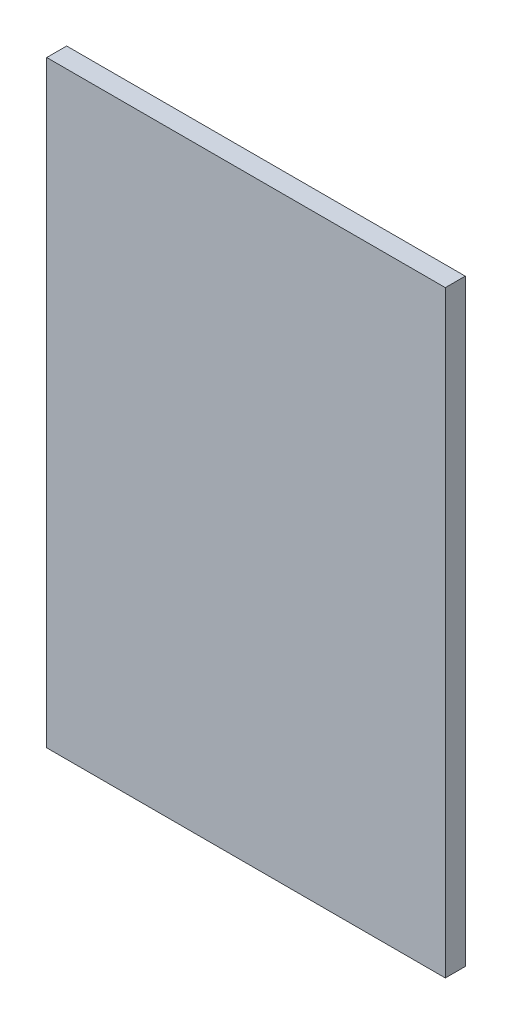
SolidWorks part; units mm, degrees
ref_plane "Front Plane" through (0, 0, 0) normal (0, 0, 1) x (1, 0, 0)
ref_plane "Top Plane" through (0, 0, 0) normal (0, 1, 0) x (1, 0, 0)
ref_plane "Right Plane" through (0, 0, 0) normal (1, 0, 0) x (0, 0, -1)
sketch "Sketch1" plane through (0, 0, 0) normal (0, 0, 1) x (1, 0, 0)
  line L1 (0, 0) -> (200, 0)
  line L2 (0, 0) -> (0, 300)
  line L3 (0, 300) -> (200, 300)
  line L4 (200, 0) -> (200, 300)
  dimension "D1" = 200
  dimension "D2" = 300
extrude "Boss-Extrude1" add sketch "Sketch1" along normal blind 10
sketch "Sketch2" plane through (0, 0, 10) normal (0, 0, 1) x (1, 0, 0)
  line L0 (100, 300) -> (100, 0) construction
  line L1 (200, 300) -> (0, 300) construction
  line L2 (0, 0) -> (200, 0) construction
sketch "Sketch3" plane through (0, 0, 10) normal (0, 0, 1) x (1, 0, 0)
  circle A0 centre (100, 99.6059) radius 4.45
  circle A3 centre (100, 139.6059) radius 4.45
  dimension "D1" = 8.9
  dimension "D2" = 8.9
extrude "Cut-Extrude1" [suppressed] cut sketch "Sketch3" against normal blind 10
sketch "Sketch5" plane through (0, 0, 10) normal (0, 0, 1) x (1, 0, 0)
  line L15 (91.536, 226.6059) -> (43.8, 226.6059)
  line L16 (29.8, 212.6059) -> (29.8, 153.11)
  line L17 (32.4795, 143.11) -> (66.2568, 84.6059)
  line L24 (74.9171, 79.6059) -> (125.0829, 79.6059)
  line L25 (133.7432, 84.6059) -> (167.5205, 143.11)
  line L26 (170.2, 153.11) -> (170.2, 212.6059)
  line L27 (156.2, 226.6059) -> (108.464, 226.6059)
  arc A12 (66.2568, 84.6059) -> (74.9171, 79.6059) centre (74.9171, 89.6059) ccw
  arc A15 (100, 223.7576) -> (91.536, 226.6059) centre (91.536, 212.6059) ccw
  arc A16 (43.8, 226.6059) -> (29.8, 212.6059) centre (43.8, 212.6059) ccw
  arc A17 (29.8, 153.11) -> (32.4795, 143.11) centre (49.8, 153.11) ccw
  arc A25 (125.0829, 79.6059) -> (133.7432, 84.6059) centre (125.0829, 89.6059) ccw
  arc A26 (167.5205, 143.11) -> (170.2, 153.11) centre (150.2, 153.11) ccw
  arc A27 (170.2, 212.6059) -> (156.2, 226.6059) centre (156.2, 212.6059) ccw
  arc A28 (108.464, 226.6059) -> (100, 223.7576) centre (108.464, 212.6059) ccw
extrude "Cut-Extrude2" [suppressed] cut sketch "Sketch5" against normal blind 2
ref_plane "Plane1" through (0, 0, 9.5) normal (0, 0, 1) x (1, 0, 0)
sketch "Sketch6" plane through (0, 0, 9.5) normal (0, 0, 1) x (1, 0, 0)
  line L0 (100, 300) -> (100, 0) construction
  line L1 (20, 20) -> (100, 20)
  line L2 (20, 20) -> (20, 55)
  line L3 (20, 55) -> (100, 55)
  line L4 (0, 300) -> (0, 0)
  line L5 (0, 0) -> (200, 0)
  line L6 (200, 0) -> (200, 300)
  line L7 (200, 300) -> (0, 300)
  line L8 (0, 300) -> (0, 0)
  line L9 (0, 0) -> (200, 0)
  line L10 (200, 0) -> (200, 300)
  line L11 (200, 300) -> (0, 300)
  line L12 (100, 20) -> (100, 55)
  line L13 (100, 55) -> (20, 55) construction
  line L14 (17, 20) -> (20, 20)
  line L15 (100, 17) -> (100, 20)
  line L16 (103, 20) -> (100, 20)
  line L17 (20, 17) -> (20, 20)
  line L18 (103, 55) -> (100, 55)
  line L19 (100, 58) -> (100, 55)
  line L20 (20, 59.1248) -> (20, 55)
  line L21 (20, 55) -> (17, 55)
  dimension "D2" = 3
  dimension "D3" = 3
  dimension "D4" = 3
  dimension "D5" = 3
  dimension "D6" = 3
  dimension "D1" = 0
